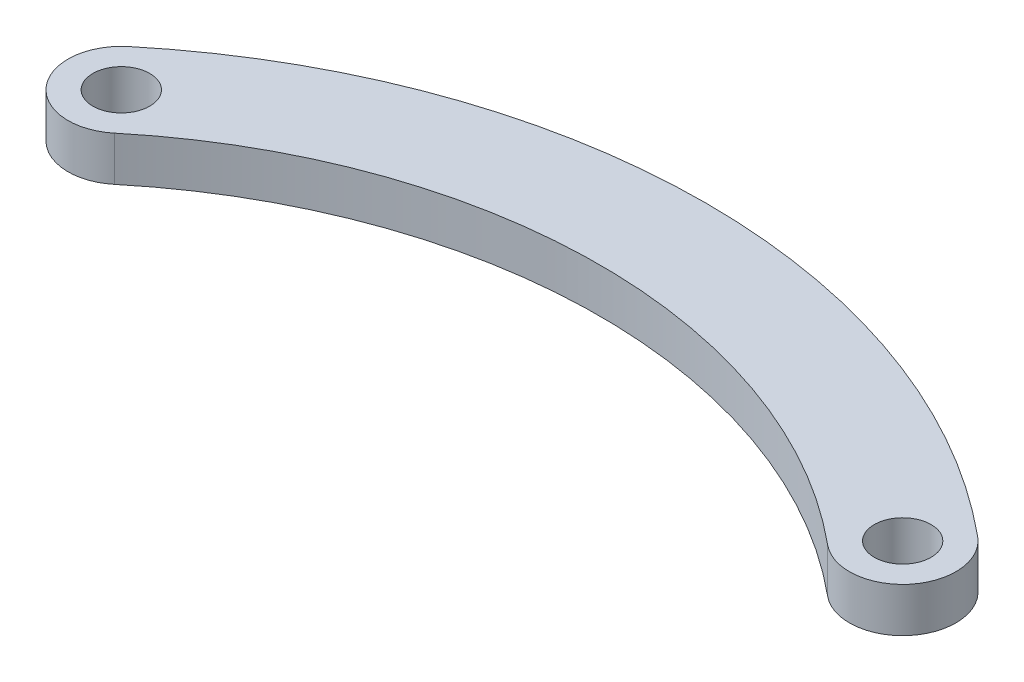
SolidWorks part; units mm, degrees
material "碳纤维"
ref_plane "前视基准面" through (0, 0, 0) normal (0, 0, 1) x (1, 0, 0)
ref_plane "上视基准面" through (0, 0, 0) normal (0, 1, 0) x (1, 0, 0)
ref_plane "右视基准面" through (0, 0, 0) normal (1, 0, 0) x (0, 0, -1)
other "Configuration Table"
ref_axis "基准轴1" through (-66.99, 0, 0) along (1, 0, 0)
ref_axis "基准轴2" through (0, 56.25, 0) along (0, -1, 0)
ref_axis "基准轴3" through (0, 0, -92.9589) along (0, 0, 1)
sketch "草图1" plane through (0, 0, 0) normal (0, 1, 0) x (1, 0, 0)
  line L0 (0, 0) -> (44, 0) construction
  circle A2 centre (0, 0) radius 1.6
  circle A3 centre (44, 0) radius 1.6
  arc A8 (0, 0) -> (44, 0) centre (22, -26.5179) cw construction
  arc A9 (45.9155, 2.3089) -> (-1.9155, 2.3089) centre (22, -26.5179) ccw
  arc A10 (42.0845, -2.3089) -> (1.9155, -2.3089) centre (22, -26.5179) ccw
  arc A11 (42.0845, -2.3089) -> (45.9155, 2.3089) centre (44, 0) ccw
  arc A12 (-1.9155, 2.3089) -> (1.9155, -2.3089) centre (0, 0) ccw
  point P1 (22, 7.9379)
  dimension "D1" = 1.6
  dimension "D2" = 3
  dimension "D3" = 44
extrude "凸台-拉伸1" add sketch "草图1" along normal blind 2.5
